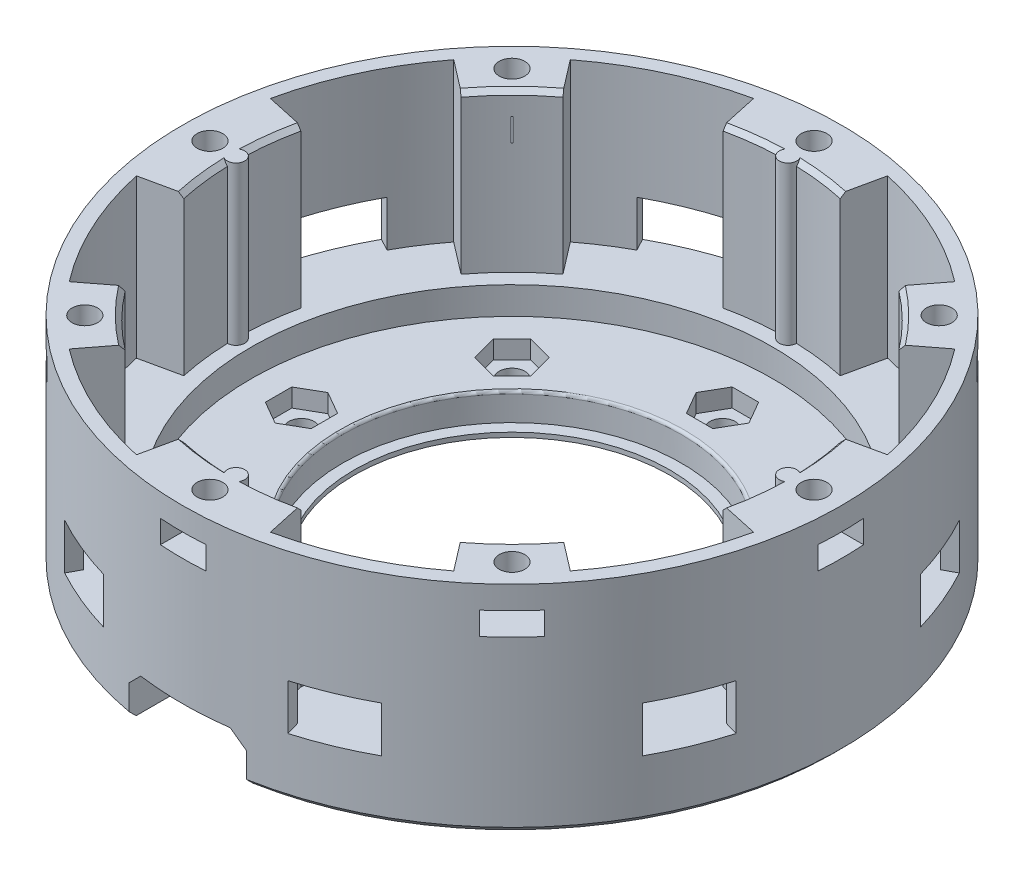
SolidWorks part; units mm, degrees
ref_plane "Front Plane" through (0, 0, 0) normal (0, 0, 1) x (1, 0, 0)
ref_plane "Top Plane" through (0, 0, 0) normal (0, 1, 0) x (1, 0, 0)
ref_plane "Right Plane" through (0, 0, 0) normal (1, 0, 0) x (0, 0, -1)
sketch "Sketch1" plane through (0, 0, 0) normal (0, 1, 0) x (1, 0, 0)
  circle A0 centre (0, 0) radius 36
  dimension "D1" = 72
extrude "Boss-Extrude1" add sketch "Sketch1" along normal blind 4
sketch "Sketch6" plane through (0, 4, 0) normal (0, 1, 0) x (1, 0, 0)
  circle A0 centre (0, 0) radius 16
  circle A1 centre (0, 0) radius 12.5
  dimension "D1" = 32
  dimension "D2" = 25
extrude "Boss-Extrude4" add sketch "Sketch6" along normal blind 0.3
sketch "Sketch7" plane through (0, 4.3, 0) normal (0, 1, 0) x (1, 0, 0)
  circle A0 centre (0, 0) radius 13.55
  circle A1 centre (0, 0) radius 16
  circle A2 centre (0, 0) radius 16
  dimension "D2" = 27.1
  dimension "D1" = 0
extrude "Boss-Extrude5" add sketch "Sketch7" along normal blind 4
sketch "Sketch2" plane through (0, 4, 0) normal (0, 1, 0) x (1, 0, 0)
  circle A0 centre (0, 0) radius 28.5
  circle A1 centre (0, 0) radius 36 construction
  circle A2 centre (0, 0) radius 36
  dimension "D1" = 57
extrude "Boss-Extrude2" add sketch "Sketch2" along normal offset from surface (5.8 mm away) 1.5 up to face at (0, 8.3, 16) offset beyond the face yes
sketch "Sketch3" plane through (0, 9.8, 0) normal (0, 1, 0) x (1, 0, 0)
  arc A0 (-0.9499, 30.135) -> (-30.135, 0.9499) centre (0, 0) ccw
  circle A1 centre (0, 0) radius 36 construction
  circle A2 centre (0, 0) radius 36
  arc A3 (-0.9499, 30.135) -> (0.9499, 30.135) centre (0, 30.15) ccw
  arc A4 (30.135, 0.9499) -> (30.135, -0.9499) centre (30.15, 0) ccw
  arc A5 (0.9499, -30.135) -> (-0.9499, -30.135) centre (0, -30.15) ccw
  arc A6 (-30.135, -0.9499) -> (-30.135, 0.9499) centre (-30.15, 0) ccw
  arc A7 (-30.135, -0.9499) -> (-0.9499, -30.135) centre (0, 0) ccw
  arc A8 (0.9499, -30.135) -> (30.135, -0.9499) centre (0, 0) ccw
  arc A9 (30.135, 0.9499) -> (0.9499, 30.135) centre (0, 0) ccw
  point P21 (0, 0)
  dimension "60.15" = 60.3
  dimension "D2" = 0.95
  dimension "D3" = 4
extrude "Boss-Extrude3" add sketch "Sketch3" along normal blind 17.25
sketch "Sketch8" plane through (0, 0, 0) normal (0, -1, 0) x (1, 0, 0)
  line L0 (0, 0) -> (0, -7.5) construction
  line L1 (-11, 7.5) -> (11, 7.5) construction
  line L2 (-11, 7.5) -> (-11, -7.5) construction
  line L3 (-11, -7.5) -> (11, -7.5) construction
  line L4 (11, 7.5) -> (11, -7.5) construction
  line L5 (-11, 7.5) -> (11, -7.5) construction
  line L6 (-11, -7.5) -> (11, 7.5) construction
  line L7 (0, 0) -> (11, 0) construction
  circle A0 centre (0, 0) radius 5.75
  circle A1 centre (-9, -5.5) radius 1.905
  circle A2 centre (9, -5.5) radius 1.905
  circle A3 centre (-9, 5.5) radius 1.905
  circle A4 centre (9, 5.5) radius 1.905
  point P0 (0, 0)
  dimension "D3" = 11.5
  dimension "D6" = 3.81
  dimension "D1" = 15
  dimension "D2" = 22
  dimension "D4" = 9
  dimension "D5" = 5.5
extrude "Cut-Extrude1" cut sketch "Sketch8" against normal up to surface (4 mm away) up to face at (0, 4, 16)
sketch "Sketch9" plane through (0, 0, 0) normal (0, -1, 0) x (1, 0, 0)
  line L0 (11, 7.5) -> (11, -7.5) construction
  line L1 (-11, -11) -> (11, -11)
  line L2 (-11, -11) -> (-11, -21)
  line L3 (-11, -21) -> (11, -21) construction
  line L4 (11, -11) -> (11, -21)
  line L5 (-11, 7.5) -> (11, 7.5) construction
  line L6 (-11, 7.5) -> (-11, -7.5) construction
  line L7 (0, 0) -> (0, -36) construction
  line L8 (-5, -27) -> (-5, -35.6511)
  line L9 (5, -27) -> (5, -35.6511)
  circle A0 centre (0, 0) radius 36 construction
  arc A1 (-11, -21) -> (-5, -27) centre (-11, -27) cw
  arc A2 (11, -21) -> (5, -27) centre (11, -27) ccw
  arc A3 (-5, -35.6511) -> (5, -35.6511) centre (0, 0) ccw
  dimension "D1" = 28.5
  dimension "D2" = 10
  dimension "D3" = 5
extrude "Cut-Extrude2" cut sketch "Sketch9" against normal blind 3
sketch "Sketch10" plane through (0, 4, 0) normal (0, 1, 0) x (1, 0, 0)
  circle A0 centre (0, 0) radius 16 construction
  circle A1 centre (0, 0) radius 28.5
  circle A2 centre (0, 0) radius 28.5
  circle A3 centre (0, 0) radius 16
  dimension "D1" = 0
extrude "Cut-Extrude3" cut sketch "Sketch10" against normal blind 2
sketch "Sketch11" plane through (0, 0, 0) normal (0, -1, 0) x (1, 0, 0)
  line L0 (-11, -11) -> (-11, -21) construction
  line L1 (11, -11) -> (-11, -11)
  line L2 (11, -11) -> (11, -10)
  line L3 (11, -10) -> (-11, -10)
  line L4 (-11, -11) -> (-11, -10)
  dimension "D1" = 1
sketch "Sketch12" plane through (0, 3, 0) normal (0, -1, 0) x (1, 0, 0)
  line L3 (11, -11.619) -> (11, -11)
  line L4 (11, -11) -> (-11, -11)
  line L5 (-11, -11) -> (-11, -11.619)
  line L6 (11, -11.619) -> (11, -11)
  line L7 (11, -11) -> (-11, -11)
  line L8 (-11, -11) -> (-11, -11.619)
  arc A1 (-11, -11.619) -> (11, -11.619) centre (0, 0) ccw
  arc A2 (-11, -11.619) -> (11, -11.619) centre (0, 0) ccw
  dimension "D1" = 0
loft "Loft1" add profiles "Sketch11", "Sketch12"
sketch "Sketch13" plane through (0, 27.05, 0) normal (0, 1, 0) x (1, 0, 0)
  line L0 (0, 0) -> (-25.4558, 25.4558) construction
  line L1 (-11, 7.5) -> (11, -7.5) construction
  line L2 (0, 0) -> (0, 36) construction
  line L3 (0, 0) -> (-7.6384, 35.1803) construction
  line L4 (0, 0) -> (-21.9154, 28.5607) construction
  line L5 (-21.0023, 27.3707) -> (-18.3542, 23.9196)
  line L6 (-7.3201, 33.7145) -> (-6.3972, 29.4635)
  line L7 (21.0023, 27.3707) -> (18.3542, 23.9196)
  line L8 (7.3201, 33.7145) -> (6.3972, 29.4635)
  line L9 (33.7145, 7.3201) -> (29.4635, 6.3972)
  line L10 (27.3707, 21.0023) -> (23.9196, 18.3542)
  line L11 (33.7145, -7.3201) -> (29.4635, -6.3972)
  line L12 (27.3707, -21.0023) -> (23.9196, -18.3542)
  line L13 (7.3201, -33.7145) -> (6.3972, -29.4635)
  line L14 (21.0023, -27.3707) -> (18.3542, -23.9196)
  line L15 (-7.3201, -33.7145) -> (-6.3972, -29.4635)
  line L16 (-21.0023, -27.3707) -> (-18.3542, -23.9196)
  line L17 (-33.7145, -7.3201) -> (-29.4635, -6.3972)
  line L18 (-27.3707, -21.0023) -> (-23.9196, -18.3542)
  line L19 (-33.7145, 7.3201) -> (-29.4635, 6.3972)
  line L20 (-27.3707, 21.0023) -> (-23.9196, 18.3542)
  circle A0 centre (0, 0) radius 36 construction
  arc A1 (-21.0023, 27.3707) -> (-7.3201, 33.7145) centre (0, 0) cw
  arc A2 (-0.9499, 30.135) -> (-30.135, 0.9499) centre (0, 0) ccw construction
  arc A3 (-18.3542, 23.9196) -> (-6.3972, 29.4635) centre (0, 0) cw
  arc A4 (21.0023, 27.3707) -> (7.3201, 33.7145) centre (0, 0) ccw
  arc A5 (18.3542, 23.9196) -> (6.3972, 29.4635) centre (0, 0) ccw
  arc A6 (23.9196, 18.3542) -> (29.4635, 6.3972) centre (0, 0) cw
  arc A7 (27.3707, 21.0023) -> (33.7145, 7.3201) centre (0, 0) cw
  arc A8 (27.3707, -21.0023) -> (33.7145, -7.3201) centre (0, 0) ccw
  arc A9 (23.9196, -18.3542) -> (29.4635, -6.3972) centre (0, 0) ccw
  arc A10 (18.3542, -23.9196) -> (6.3972, -29.4635) centre (0, 0) cw
  arc A11 (21.0023, -27.3707) -> (7.3201, -33.7145) centre (0, 0) cw
  arc A12 (-21.0023, -27.3707) -> (-7.3201, -33.7145) centre (0, 0) ccw
  arc A13 (-18.3542, -23.9196) -> (-6.3972, -29.4635) centre (0, 0) ccw
  arc A14 (-23.9196, -18.3542) -> (-29.4635, -6.3972) centre (0, 0) cw
  arc A15 (-27.3707, -21.0023) -> (-33.7145, -7.3201) centre (0, 0) cw
  arc A16 (-27.3707, 21.0023) -> (-33.7145, 7.3201) centre (0, 0) ccw
  arc A17 (-23.9196, 18.3542) -> (-29.4635, 6.3972) centre (0, 0) ccw
  point P50 (0, 0)
  dimension "D4" = 1.5
  dimension "D1" = 45
  dimension "D2" = 12.25
  dimension "D3" = 7.5
  dimension "D5" = 4
extrude "Cut-Extrude4" cut sketch "Sketch13" against normal up to surface (17.25 mm away) up to face at (0, 9.8, 28.5)
fillet "Fillet1" radius 3 2 edges at (0, 2, 16) (0, 2, 28.5)
chamfer "Chamfer3" distance 4 angle 45 1 edges at (0, 0, 36)
sketch "Sketch14" plane through (0, 2, 0) normal (0, 1, 0) x (1, 0, 0)
  line L0 (0, 0) -> (0, -25.5) construction
  line L1 (0, 0) -> (3.3284, -25.2818) construction
  line L2 (0, 0) -> (6.5999, -24.6311) construction
  line L3 (0, -25.5) -> (6.5999, -24.6311) construction
  line L4 (1.5, -18.9407) -> (1.5, -25.4558)
  line L5 (3.4533, -18.6835) -> (5.1396, -24.9767)
  line L6 (-1.5, -18.9407) -> (-1.5, -25.4558)
  line L7 (-3.4533, -18.6835) -> (-5.1396, -24.9767)
  line L8 (-6.3511, -17.9071) -> (-8.0373, -24.2002)
  line L9 (-8.1713, -17.1531) -> (-11.4289, -22.7954)
  line L10 (-10.7694, -15.6531) -> (-14.027, -21.2954)
  line L11 (-12.3324, -14.4538) -> (-16.9393, -19.0607)
  line L12 (-14.4538, -12.3324) -> (-19.0607, -16.9393)
  line L13 (-15.6531, -10.7694) -> (-21.2954, -14.027)
  line L14 (-17.1531, -8.1713) -> (-22.7954, -11.4289)
  line L15 (-17.9071, -6.3511) -> (-24.2002, -8.0373)
  line L16 (-18.6835, -3.4533) -> (-24.9767, -5.1396)
  line L17 (-18.9407, -1.5) -> (-25.4558, -1.5)
  line L18 (-18.9407, 1.5) -> (-25.4558, 1.5)
  line L19 (-18.6835, 3.4533) -> (-24.9767, 5.1396)
  line L20 (-17.9071, 6.3511) -> (-24.2002, 8.0373)
  line L21 (-17.1531, 8.1713) -> (-22.7954, 11.4289)
  line L22 (-15.6531, 10.7694) -> (-21.2954, 14.027)
  line L23 (-14.4538, 12.3324) -> (-19.0607, 16.9393)
  line L24 (-12.3324, 14.4538) -> (-16.9393, 19.0607) [skipped]
  line L25 (-10.7694, 15.6531) -> (-14.027, 21.2954) [skipped]
  line L26 (-8.1713, 17.1531) -> (-11.4289, 22.7954) [skipped]
  line L27 (-6.3511, 17.9071) -> (-8.0373, 24.2002) [skipped]
  line L28 (-3.4533, 18.6835) -> (-5.1396, 24.9767) [skipped]
  line L29 (-1.5, 18.9407) -> (-1.5, 25.4558) [skipped]
  line L30 (1.5, 18.9407) -> (1.5, 25.4558) [skipped]
  line L31 (3.4533, 18.6835) -> (5.1396, 24.9767) [skipped]
  line L32 (6.3511, 17.9071) -> (8.0373, 24.2002) [skipped]
  line L33 (8.1713, 17.1531) -> (11.4289, 22.7954) [skipped]
  line L34 (10.7694, 15.6531) -> (14.027, 21.2954) [skipped]
  line L35 (12.3324, 14.4538) -> (16.9393, 19.0607) [skipped]
  line L36 (14.4538, 12.3324) -> (19.0607, 16.9393)
  line L37 (15.6531, 10.7694) -> (21.2954, 14.027)
  line L38 (17.1531, 8.1713) -> (22.7954, 11.4289)
  line L39 (17.9071, 6.3511) -> (24.2002, 8.0373)
  line L40 (18.6835, 3.4533) -> (24.9767, 5.1396)
  line L41 (18.9407, 1.5) -> (25.4558, 1.5)
  line L42 (18.9407, -1.5) -> (25.4558, -1.5)
  line L43 (18.6835, -3.4533) -> (24.9767, -5.1396)
  line L44 (17.9071, -6.3511) -> (24.2002, -8.0373)
  line L45 (17.1531, -8.1713) -> (22.7954, -11.4289)
  line L46 (15.6531, -10.7694) -> (21.2954, -14.027)
  line L47 (14.4538, -12.3324) -> (19.0607, -16.9393)
  line L48 (12.3324, -14.4538) -> (16.9393, -19.0607)
  line L49 (10.7694, -15.6531) -> (14.027, -21.2954)
  line L50 (8.1713, -17.1531) -> (11.4289, -22.7954)
  line L51 (6.3511, -17.9071) -> (8.0373, -24.2002)
  arc A0 (-5.369, 24.9284) -> (5.369, 24.9284) centre (0, 0) ccw construction
  arc A1 (-11, 15.4919) -> (11, 15.4919) centre (0, 0) ccw construction
  arc A2 (1.5, -18.9407) -> (3.4533, -18.6835) centre (0, 0) ccw
  arc A3 (1.5, -25.4558) -> (5.1396, -24.9767) centre (0, 0) ccw
  arc A4 (-5.1396, -24.9767) -> (-1.5, -25.4558) centre (0, 0) ccw
  arc A5 (-3.4533, -18.6835) -> (-1.5, -18.9407) centre (0, 0) ccw
  arc A6 (-11.4289, -22.7954) -> (-8.0373, -24.2002) centre (0, 0) ccw
  arc A7 (-8.1713, -17.1531) -> (-6.3511, -17.9071) centre (0, 0) ccw
  arc A8 (-16.9393, -19.0607) -> (-14.027, -21.2954) centre (0, 0) ccw
  arc A9 (-12.3324, -14.4538) -> (-10.7694, -15.6531) centre (0, 0) ccw
  arc A10 (-21.2954, -14.027) -> (-19.0607, -16.9393) centre (0, 0) ccw
  arc A11 (-15.6531, -10.7694) -> (-14.4538, -12.3324) centre (0, 0) ccw
  arc A12 (-24.2002, -8.0373) -> (-22.7954, -11.4289) centre (0, 0) ccw
  arc A13 (-17.9071, -6.3511) -> (-17.1531, -8.1713) centre (0, 0) ccw
  arc A14 (-25.4558, -1.5) -> (-24.9767, -5.1396) centre (0, 0) ccw
  arc A15 (-18.9407, -1.5) -> (-18.6835, -3.4533) centre (0, 0) ccw
  arc A16 (-24.9767, 5.1396) -> (-25.4558, 1.5) centre (0, 0) ccw
  arc A17 (-18.6835, 3.4533) -> (-18.9407, 1.5) centre (0, 0) ccw
  arc A18 (-22.7954, 11.4289) -> (-24.2002, 8.0373) centre (0, 0) ccw
  arc A19 (-17.1531, 8.1713) -> (-17.9071, 6.3511) centre (0, 0) ccw
  arc A20 (-19.0607, 16.9393) -> (-21.2954, 14.027) centre (0, 0) ccw
  arc A21 (-14.4538, 12.3324) -> (-15.6531, 10.7694) centre (0, 0) ccw
  arc A22 (-14.027, 21.2954) -> (-16.9393, 19.0607) centre (0, 0) ccw [skipped]
  arc A23 (-10.7694, 15.6531) -> (-12.3324, 14.4538) centre (0, 0) ccw [skipped]
  arc A24 (-8.0373, 24.2002) -> (-11.4289, 22.7954) centre (0, 0) ccw [skipped]
  arc A25 (-6.3511, 17.9071) -> (-8.1713, 17.1531) centre (0, 0) ccw [skipped]
  arc A26 (-1.5, 25.4558) -> (-5.1396, 24.9767) centre (0, 0) ccw [skipped]
  arc A27 (-1.5, 18.9407) -> (-3.4533, 18.6835) centre (0, 0) ccw [skipped]
  arc A28 (5.1396, 24.9767) -> (1.5, 25.4558) centre (0, 0) ccw [skipped]
  arc A29 (3.4533, 18.6835) -> (1.5, 18.9407) centre (0, 0) ccw [skipped]
  arc A30 (11.4289, 22.7954) -> (8.0373, 24.2002) centre (0, 0) ccw [skipped]
  arc A31 (8.1713, 17.1531) -> (6.3511, 17.9071) centre (0, 0) ccw [skipped]
  arc A32 (16.9393, 19.0607) -> (14.027, 21.2954) centre (0, 0) ccw [skipped]
  arc A33 (12.3324, 14.4538) -> (10.7694, 15.6531) centre (0, 0) ccw [skipped]
  arc A34 (21.2954, 14.027) -> (19.0607, 16.9393) centre (0, 0) ccw
  arc A35 (15.6531, 10.7694) -> (14.4538, 12.3324) centre (0, 0) ccw
  arc A36 (24.2002, 8.0373) -> (22.7954, 11.4289) centre (0, 0) ccw
  arc A37 (17.9071, 6.3511) -> (17.1531, 8.1713) centre (0, 0) ccw
  arc A38 (25.4558, 1.5) -> (24.9767, 5.1396) centre (0, 0) ccw
  arc A39 (18.9407, 1.5) -> (18.6835, 3.4533) centre (0, 0) ccw
  arc A40 (24.9767, -5.1396) -> (25.4558, -1.5) centre (0, 0) ccw
  arc A41 (18.6835, -3.4533) -> (18.9407, -1.5) centre (0, 0) ccw
  arc A42 (22.7954, -11.4289) -> (24.2002, -8.0373) centre (0, 0) ccw
  arc A43 (17.1531, -8.1713) -> (17.9071, -6.3511) centre (0, 0) ccw
  arc A44 (19.0607, -16.9393) -> (21.2954, -14.027) centre (0, 0) ccw
  arc A45 (14.4538, -12.3324) -> (15.6531, -10.7694) centre (0, 0) ccw
  arc A46 (14.027, -21.2954) -> (16.9393, -19.0607) centre (0, 0) ccw
  arc A47 (10.7694, -15.6531) -> (12.3324, -14.4538) centre (0, 0) ccw
  arc A48 (8.0373, -24.2002) -> (11.4289, -22.7954) centre (0, 0) ccw
  arc A49 (6.3511, -17.9071) -> (8.1713, -17.1531) centre (0, 0) ccw
  point P9 (3.2999, -25.0656)
  point P88 (0, 0)
  point P113 (0, 0)
  dimension "D1" = 15
  dimension "D2" = 1.5
  dimension "D3" = 24
extrude "Cut-Extrude5" cut sketch "Sketch14" against normal through all
sketch "Sketch15" plane through (0, 27.05, 0) normal (0, 1, 0) x (1, 0, 0)
  circle A0 centre (0, 33) radius 1.4
  circle A1 centre (0, 0) radius 36 construction
  circle A2 centre (23.3345, 23.3345) radius 1.4
  circle A3 centre (33, 0) radius 1.4
  circle A4 centre (23.3345, -23.3345) radius 1.4
  circle A5 centre (0, -33) radius 1.4
  circle A6 centre (-23.3345, -23.3345) radius 1.4
  circle A7 centre (-33, 0) radius 1.4
  circle A8 centre (-23.3345, 23.3345) radius 1.4
  point P5 (0, 36)
  point P23 (0, 0)
  dimension "D1" = 2.8
  dimension "D2" = 3
  dimension "D3" = 8
extrude "Cut-Extrude6" cut sketch "Sketch15" against normal blind 5
chamfer "Chamfer4" distance 0.3 angle 45 1 edges at (0, 4, 5.75)
sketch "Sketch16" plane through (0, 3, 0) normal (0, -1, 0) x (1, 0, 0)
  line L0 (-5, -28.058) -> (-5, -34.641) construction
  line L1 (5, -28.058) -> (-5, -28.058)
  line L2 (5, -28.058) -> (5, -36)
  line L3 (5, -36) -> (-5, -36)
  line L4 (-5, -28.058) -> (-5, -36)
  circle A0 centre (0, 0) radius 36 construction
extrude "Cut-Extrude7" cut sketch "Sketch16" against normal blind 2
chamfer "Chamfer5" distance 0.5 angle 45 12 edges at (-21.3193, 27.05, 21.3193) (-3.6888, 27.05, 29.9235) (3.6888, 27.05, 29.9235) (21.3193, 27.05, 21.3193) (29.9235, 27.05, 3.6888) (29.9235, 27.05, -3.6888) (21.3193, 27.05, -21.3193) (3.6888, 27.05, -29.9235) (-3.6888, 27.05, -29.9235) (-21.3193, 27.05, -21.3193) (-29.9235, 27.05, 3.6888) (-29.9235, 27.05, -3.6888)
sketch "Sketch17" plane through (0, 9.8, 0) normal (0, 1, 0) x (1, 0, 0)
  line L0 (-17.3102, 31.5651) -> (-16.5889, 30.2499)
  line L1 (-9.6598, 33.1201) -> (-10.0798, 34.5601)
  line L2 (0, 0) -> (0, 36) construction
  line L3 (0, 0) -> (-13.2026, 31.8738) construction
  line L4 (10.0798, 34.5601) -> (9.6598, 33.1201)
  line L5 (16.5889, 30.2499) -> (17.3102, 31.5651)
  line L6 (31.5651, 17.3102) -> (30.2499, 16.5889)
  line L7 (33.1201, 9.6598) -> (34.5601, 10.0798)
  line L8 (34.5601, -10.0798) -> (33.1201, -9.6598)
  line L9 (30.2499, -16.5889) -> (31.5651, -17.3102)
  line L10 (17.3102, -31.5651) -> (16.5889, -30.2499)
  line L11 (9.6598, -33.1201) -> (10.0798, -34.5601)
  line L12 (-10.0798, -34.5601) -> (-9.6598, -33.1201)
  line L13 (-16.5889, -30.2499) -> (-17.3102, -31.5651)
  line L14 (-31.5651, -17.3102) -> (-30.2499, -16.5889)
  line L15 (-33.1201, -9.6598) -> (-34.5601, -10.0798)
  line L16 (-34.5601, 10.0798) -> (-33.1201, 9.6598)
  line L17 (-30.2499, 16.5889) -> (-31.5651, 17.3102)
  arc A0 (-16.5889, 30.2499) -> (-9.6598, 33.1201) centre (0, 0) cw
  arc A1 (-7.3201, 33.7145) -> (-21.0023, 27.3707) centre (0, 0) ccw construction
  arc A2 (-17.3102, 31.5651) -> (-10.0798, 34.5601) centre (0, 0) cw
  circle A3 centre (0, 0) radius 36 construction
  arc A4 (-7.3201, 33.7145) -> (-21.0023, 27.3707) centre (0, 0) ccw construction
  arc A5 (9.6598, 33.1201) -> (16.5889, 30.2499) centre (0, 0) cw
  arc A6 (10.0798, 34.5601) -> (17.3102, 31.5651) centre (0, 0) cw
  arc A7 (30.2499, 16.5889) -> (33.1201, 9.6598) centre (0, 0) cw
  arc A8 (31.5651, 17.3102) -> (34.5601, 10.0798) centre (0, 0) cw
  arc A9 (33.1201, -9.6598) -> (30.2499, -16.5889) centre (0, 0) cw
  arc A10 (34.5601, -10.0798) -> (31.5651, -17.3102) centre (0, 0) cw
  arc A11 (16.5889, -30.2499) -> (9.6598, -33.1201) centre (0, 0) cw
  arc A12 (17.3102, -31.5651) -> (10.0798, -34.5601) centre (0, 0) cw
  arc A13 (-9.6598, -33.1201) -> (-16.5889, -30.2499) centre (0, 0) cw
  arc A14 (-10.0798, -34.5601) -> (-17.3102, -31.5651) centre (0, 0) cw
  arc A15 (-30.2499, -16.5889) -> (-33.1201, -9.6598) centre (0, 0) cw
  arc A16 (-31.5651, -17.3102) -> (-34.5601, -10.0798) centre (0, 0) cw
  arc A17 (-33.1201, 9.6598) -> (-30.2499, 16.5889) centre (0, 0) cw
  arc A18 (-34.5601, 10.0798) -> (-31.5651, 17.3102) centre (0, 0) cw
  point P48 (0, 0)
  dimension "D1" = 22.5
  dimension "D2" = 7.5
  dimension "D3" = 8
extrude "Cut-Extrude8" cut sketch "Sketch17" along normal blind 5
sketch "Sketch18" plane through (0, 22.05, 0) normal (0, 1, 0) x (1, 0, 0)
  line L0 (-2.5, 34.4434) -> (-2.5, 36)
  line L1 (0, 35.8868) -> (-2.5, 34.4434) construction
  line L2 (-2.5, 34.4434) -> (-2.5, 31.5566)
  line L3 (-2.5, 31.5566) -> (0, 30.1132)
  line L4 (0, 30.1132) -> (2.5, 31.5566)
  line L5 (2.5, 31.5566) -> (2.5, 34.4434)
  line L6 (2.5, 34.4434) -> (0, 35.8868) construction
  line L7 (-2.5, 36) -> (2.5, 36)
  line L8 (2.5, 36) -> (2.5, 34.4434)
  line L9 (23.6881, 27.2236) -> (27.2236, 23.6881)
  line L10 (27.2236, 23.6881) -> (26.1229, 22.5874)
  line L11 (24.0817, 20.5461) -> (26.1229, 22.5874)
  line L12 (21.2933, 21.2933) -> (24.0817, 20.5461)
  line L13 (20.5461, 24.0817) -> (21.2933, 21.2933)
  line L14 (22.5874, 26.1229) -> (20.5461, 24.0817)
  line L15 (22.5874, 26.1229) -> (23.6881, 27.2236)
  line L16 (36, 2.5) -> (36, -2.5)
  line L17 (36, -2.5) -> (34.4434, -2.5)
  line L18 (31.5566, -2.5) -> (34.4434, -2.5)
  line L19 (30.1132, 0) -> (31.5566, -2.5)
  line L20 (31.5566, 2.5) -> (30.1132, 0)
  line L21 (34.4434, 2.5) -> (31.5566, 2.5)
  line L22 (34.4434, 2.5) -> (36, 2.5)
  line L23 (27.2236, -23.6881) -> (23.6881, -27.2236)
  line L24 (23.6881, -27.2236) -> (22.5874, -26.1229)
  line L25 (20.5461, -24.0817) -> (22.5874, -26.1229)
  line L26 (21.2933, -21.2933) -> (20.5461, -24.0817)
  line L27 (24.0817, -20.5461) -> (21.2933, -21.2933)
  line L28 (26.1229, -22.5874) -> (24.0817, -20.5461)
  line L29 (26.1229, -22.5874) -> (27.2236, -23.6881)
  line L30 (2.5, -36) -> (-2.5, -36)
  line L31 (-2.5, -36) -> (-2.5, -34.4434)
  line L32 (-2.5, -31.5566) -> (-2.5, -34.4434)
  line L33 (0, -30.1132) -> (-2.5, -31.5566)
  line L34 (2.5, -31.5566) -> (0, -30.1132)
  line L35 (2.5, -34.4434) -> (2.5, -31.5566)
  line L36 (2.5, -34.4434) -> (2.5, -36)
  line L37 (-23.6881, -27.2236) -> (-27.2236, -23.6881)
  line L38 (-27.2236, -23.6881) -> (-26.1229, -22.5874)
  line L39 (-24.0817, -20.5461) -> (-26.1229, -22.5874)
  line L40 (-21.2933, -21.2933) -> (-24.0817, -20.5461)
  line L41 (-20.5461, -24.0817) -> (-21.2933, -21.2933)
  line L42 (-22.5874, -26.1229) -> (-20.5461, -24.0817)
  line L43 (-22.5874, -26.1229) -> (-23.6881, -27.2236)
  line L44 (-36, -2.5) -> (-36, 2.5)
  line L45 (-36, 2.5) -> (-34.4434, 2.5)
  line L46 (-31.5566, 2.5) -> (-34.4434, 2.5)
  line L47 (-30.1132, 0) -> (-31.5566, 2.5)
  line L48 (-31.5566, -2.5) -> (-30.1132, 0)
  line L49 (-34.4434, -2.5) -> (-31.5566, -2.5)
  line L50 (-34.4434, -2.5) -> (-36, -2.5)
  line L51 (-27.2236, 23.6881) -> (-23.6881, 27.2236)
  line L52 (-23.6881, 27.2236) -> (-22.5874, 26.1229)
  line L53 (-20.5461, 24.0817) -> (-22.5874, 26.1229)
  line L54 (-21.2933, 21.2933) -> (-20.5461, 24.0817)
  line L55 (-24.0817, 20.5461) -> (-21.2933, 21.2933)
  line L56 (-26.1229, 22.5874) -> (-24.0817, 20.5461)
  line L57 (-26.1229, 22.5874) -> (-27.2236, 23.6881)
  circle A0 centre (0, 33) radius 2.5 construction
  circle A1 centre (0, 0) radius 36 construction
  point P65 (0, 0)
  dimension "D1" = 5
  dimension "D2" = 8
extrude "Cut-Extrude9" cut sketch "Sketch18" along normal blind 2.5
sketch "Sketch19" plane through (0, 0, 0) normal (0, -1, 0) x (1, 0, 0)
  line L1 (-3.05, -1.833) -> (5.45, -1.833)
  line L2 (-3.05, -1.833) -> (-3.05, -16)
  line L3 (-3.05, -16) -> (5.45, -16)
  line L4 (5.45, -1.833) -> (5.45, -16)
  circle A0 centre (0, 0) radius 5.75 construction
  arc A1 (-11, -11.619) -> (11, -11.619) centre (0, 0) ccw construction
  point P8 (1.2, -1.833)
  dimension "D1" = 8.5
  dimension "D2" = 1.2
extrude "Cut-Extrude10" cut sketch "Sketch19" against normal blind 2
ref_plane "Plane1" through (0, 6.8, 0) normal (0, 1, 0) x (1, 0, 0)
sketch "Sketch20" plane through (0, 6.8, 0) normal (0, 1, 0) x (1, 0, 0)
  circle A0 centre (0, 0) radius 36
extrude "Cut-Extrude11" cut sketch "Sketch20" against normal blind 10
sketch "Sketch21" plane through (0, 6.8, 0) normal (0, -1, 0) x (1, 0, 0)
  line L0 (0, 0) -> (0, 36) construction
  circle A0 centre (0, 0) radius 36 construction
sketch "Sketch23" plane through (0, 6.8, 0) normal (0, -1, 0) x (1, 0, 0)
  line L0 (0, 0) -> (0, -17.25) construction
  line L1 (-1, -17.221) -> (-1, -27.3875)
  line L2 (-1, -27.3875) -> (-4, -27.3875)
  line L3 (-4, -27.3875) -> (-4, -21.8875)
  line L4 (-19.2691, -11.125) -> (-21.0011, -12.125)
  line L5 (-8.5, -22.7115) -> (-8.5, -27.2029)
  line L6 (-8.5, -27.2029) -> (8.5, -27.2029) construction
  line L7 (19.2691, -11.125) -> (21.0011, -12.125)
  line L8 (8.5, -22.7115) -> (8.5, -27.2029)
  line L9 (4, -27.3875) -> (4, -21.8875) construction
  line L10 (1, -27.3875) -> (4, -27.3875)
  line L11 (1, -17.221) -> (1, -27.3875)
  line L12 (4, -27.3875) -> (6, -27.3875)
  line L13 (6, -27.3875) -> (6, -21.4257)
  circle A0 centre (0, 0) radius 36 construction
  circle A1 centre (0, 0) radius 36
  circle A2 centre (0, 0) radius 17.25 construction
  arc A3 (-4, -21.8875) -> (-19.2691, -11.125) centre (0, 0) cw
  arc A4 (-21.0011, -12.125) -> (-8.5, -22.7115) centre (0, 0) ccw
  arc A5 (21.0011, -12.125) -> (8.5, -22.7115) centre (0, 0) cw
  arc A6 (4, -21.8875) -> (19.2691, -11.125) centre (0, 0) ccw construction
  arc A7 (-1, -17.221) -> (1, -17.221) centre (0, 0) cw
  circle A8 centre (0, 0) radius 28.5 construction
  arc A9 (6, -21.4257) -> (19.2691, -11.125) centre (0, 0) ccw
  arc A10 (-8.5, -27.2029) -> (8.5, -27.2029) centre (0, 0) ccw
  point P19 (0, -27.2029)
  point P26 (-8.4147, -22.5029)
  point P29 (8.975, -27.0499)
  point P30 (-8.5, -27.3875)
  point P31 (-8.5, -29.4577)
  point P32 (-8.5, -27.2029)
  dimension "D1" = 34.5
  dimension "D4" = 5
  dimension "D7" = 2
  dimension "D2" = 2
  dimension "D3" = 5.5
  dimension "D5" = 8
  dimension "D6" = 2
  dimension "D8" = 2.5
  dimension "D9" = 60
extrude "Boss-Extrude6" [suppressed] add sketch "Sketch23" along normal blind 5
sketch "Sketch25" [suppressed] plane through (0, 6.8, 0) normal (0, 1, 0) x (1, 0, 0)
  circle A0 centre (0, 0) radius 18.55
  dimension "D1" = 37.1
extrude "Cut-Extrude12" [suppressed] cut sketch "Sketch25" against normal blind 3
sketch "Sketch26" [suppressed] plane through (6, 0, 0) normal (1, 0, 0) x (0, 0, -1)
  line L0 (24.4066, 1.8) -> (24.4066, 6.8) construction
  line L1 (21.4257, 1.8) -> (27.3875, 1.8) construction
  line L2 (21.4257, 6.8) -> (27.3875, 6.8) construction
  circle A0 centre (24.4066, 4.3) radius 1.9304
  dimension "D1" = 3.8608
extrude "Cut-Extrude13" [suppressed] cut sketch "Sketch26" against normal up to surface (5 mm away)
ref_plane "Plane2" through (-6.5, 0, 0) normal (1, 0, 0) x (0, 0, -1)
sketch "Sketch27" [suppressed] plane through (-6.5, 0, 0) normal (1, 0, 0) x (0, 0, -1)
  line L0 (21.4762, 4.3) -> (21.4762, 0.3)
  line L1 (21.4762, 0.3) -> (27.337, 0.3)
  line L2 (27.337, 0.3) -> (27.337, 4.3)
  circle A0 centre (24.4066, 4.3) radius 1.9304 construction
  circle A1 centre (24.4066, 4.3) radius 1.9304 construction
  circle A2 centre (24.4066, 4.3) radius 2.9304 construction
  arc A3 (21.4762, 4.3) -> (27.337, 4.3) centre (24.4066, 4.3) cw
  point P6 (24.4066, 4.3)
  point P11 (27.3312, 4.4839)
  dimension "D2" = 4
  dimension "D1" = 1
ref_plane "Plane3" [suppressed] through (0, 0, -24.4066) normal (0, 0, 1) x (1, 0, 0)
sketch "Sketch28" [suppressed] plane through (0, 0, -24.4066) normal (0, 0, 1) x (1, 0, 0)
  line L0 (-6.5, 4.3) -> (-26.409, -2.9463)
  line L3 (-6.5, 2.3696) -> (-6.5, 6.2304) construction
  point P4 (0, 0)
  point P5 (-31.9816, -2.5278)
  point P6 (-26.9648, -1.1835)
  dimension "D1" = 70
sweep "Cut-Sweep1" [suppressed] cut profiles "Sketch27" path "Sketch28"
mirror "Mirror1" [suppressed] about plane through (0, 0, 0) normal (1, 0, 0)
sketch "Sketch29" [suppressed] plane through (-4, 0, 0) normal (-1, 0, 0) x (0, 0, 1)
  circle A0 centre (-24.4066, 4.3) radius 1.35
  circle A1 centre (-24.4066, 4.3) radius 1.9304 construction
  dimension "D1" = 2.7
extrude "Cut-Extrude14" [suppressed] cut sketch "Sketch29" against normal up to surface (3 mm away)
sketch "Sketch30" [suppressed] plane through (0, 1.8, 0) normal (0, -1, 0) x (1, 0, 0)
  line L0 (-19.799, 19.799) -> (0, 0) construction
  line L1 (0, 0) -> (0, 36) construction
  line L2 (0, 0) -> (-19.799, 19.799) construction
  line L3 (0, 0) -> (-28, 0) construction
  line L4 (0, 0) -> (0, 36) construction
  circle A0 centre (0, 0) radius 28 construction
  circle A1 centre (-19.799, 19.799) radius 1.9304
  circle A2 centre (-28, 0) radius 1.9304
  circle A3 centre (-19.799, -19.799) radius 1.9304
  circle A4 centre (19.799, -19.799) radius 1.9304
  circle A5 centre (19.799, 19.799) radius 1.9304
  circle A6 centre (28, 0) radius 1.9304
  dimension "D1" = 56
  dimension "D2" = 3.8608
  dimension "D3" = 45
  dimension "D5" = 45
  dimension "D4" = 3
extrude "Cut-Extrude15" [suppressed] cut sketch "Sketch30" against normal blind 3.5
sketch "Sketch31" plane through (0, 6.8, 0) normal (0, -1, 0) x (1, 0, 0)
  circle A0 centre (0, 0) radius 36
  circle A1 centre (0, 0) radius 36 construction
  circle A2 centre (0, 0) radius 17.25
  dimension "D1" = 34.5
extrude "Boss-Extrude7" add sketch "Sketch31" along normal blind 3.5
sketch "Sketch32" plane through (0, 6.8, 0) normal (0, 1, 0) x (1, 0, 0)
  circle A0 centre (0, 0) radius 18.525
  dimension "D1" = 37.05
extrude "Cut-Extrude16" cut sketch "Sketch32" against normal blind 3
fillet "Fillet2" radius 0.3 1 edges at (0, 6.8, 18.525)
sketch "Sketch33" plane through (0, 3.3, 0) normal (0, -1, 0) x (1, 0, 0)
  line L0 (-16.2635, 16.2635) -> (0, 0) construction
  line L1 (0, 0) -> (0, 36) construction
  line L2 (0, 0) -> (-16.2635, 16.2635) construction
  line L3 (0, 0) -> (-23, 0) construction
  circle A0 centre (0, 0) radius 23 construction
  circle A1 centre (-16.2635, 16.2635) radius 1.4
  circle A2 centre (-23, 0) radius 1.4
  circle A3 centre (-16.2635, -16.2635) radius 1.4
  circle A4 centre (16.2635, -16.2635) radius 1.4
  circle A5 centre (23, 0) radius 1.4
  circle A6 centre (16.2635, 16.2635) radius 1.4
  circle A8 centre (0, -23) radius 1.4
  dimension "D1" = 46
  dimension "D2" = 2.8
  dimension "D3" = 45
  dimension "D5" = 45
  dimension "D4" = 3
extrude "Cut-Extrude17" cut sketch "Sketch33" against normal blind 3.5
sketch "Sketch34" plane through (0, 6.8, 0) normal (0, 1, 0) x (1, 0, 0)
  line L0 (0, 0) -> (-16.2635, 16.2635) construction
  line L1 (1.4434, 20.5) -> (2.8868, 23)
  line L2 (-13.4751, 15.5163) -> (-14.2222, 18.3047)
  line L3 (-14.2222, 18.3047) -> (-17.0106, 19.0518)
  line L4 (-17.0106, 19.0518) -> (-19.0518, 17.0106)
  line L5 (-19.0518, 17.0106) -> (-18.3047, 14.2222)
  line L6 (-18.3047, 14.2222) -> (-15.5163, 13.4751)
  line L7 (-15.5163, 13.4751) -> (-13.4751, 15.5163)
  line L8 (2.8868, 23) -> (1.4434, 25.5)
  line L9 (1.4434, 25.5) -> (-1.4434, 25.5)
  line L10 (-1.4434, 25.5) -> (-2.8868, 23)
  line L11 (-2.8868, 23) -> (-1.4434, 20.5)
  line L12 (-1.4434, 20.5) -> (1.4434, 20.5)
  line L79 (15.5163, 13.4751) -> (18.3047, 14.2222)
  line L80 (18.3047, 14.2222) -> (19.0518, 17.0106)
  line L81 (19.0518, 17.0106) -> (17.0106, 19.0518)
  line L82 (17.0106, 19.0518) -> (14.2222, 18.3047)
  line L83 (14.2222, 18.3047) -> (13.4751, 15.5163)
  line L84 (13.4751, 15.5163) -> (15.5163, 13.4751)
  line L85 (20.5, -1.4434) -> (23, -2.8868)
  line L86 (23, -2.8868) -> (25.5, -1.4434)
  line L87 (25.5, -1.4434) -> (25.5, 1.4434)
  line L88 (25.5, 1.4434) -> (23, 2.8868)
  line L89 (23, 2.8868) -> (20.5, 1.4434)
  line L90 (20.5, 1.4434) -> (20.5, -1.4434)
  line L91 (13.4751, -15.5163) -> (14.2222, -18.3047)
  line L92 (14.2222, -18.3047) -> (17.0106, -19.0518)
  line L93 (17.0106, -19.0518) -> (19.0518, -17.0106)
  line L94 (19.0518, -17.0106) -> (18.3047, -14.2222)
  line L95 (18.3047, -14.2222) -> (15.5163, -13.4751)
  line L96 (15.5163, -13.4751) -> (13.4751, -15.5163)
  line L97 (-1.4434, -20.5) -> (-2.8868, -23) [skipped]
  line L98 (-2.8868, -23) -> (-1.4434, -25.5) [skipped]
  line L99 (-1.4434, -25.5) -> (1.4434, -25.5) [skipped]
  line L100 (1.4434, -25.5) -> (2.8868, -23) [skipped]
  line L101 (2.8868, -23) -> (1.4434, -20.5) [skipped]
  line L102 (1.4434, -20.5) -> (-1.4434, -20.5) [skipped]
  line L103 (-15.5163, -13.4751) -> (-18.3047, -14.2222)
  line L104 (-18.3047, -14.2222) -> (-19.0518, -17.0106)
  line L105 (-19.0518, -17.0106) -> (-17.0106, -19.0518)
  line L106 (-17.0106, -19.0518) -> (-14.2222, -18.3047)
  line L107 (-14.2222, -18.3047) -> (-13.4751, -15.5163)
  line L108 (-13.4751, -15.5163) -> (-15.5163, -13.4751)
  line L109 (-20.5, 1.4434) -> (-23, 2.8868)
  line L110 (-23, 2.8868) -> (-25.5, 1.4434)
  line L111 (-25.5, 1.4434) -> (-25.5, -1.4434)
  line L112 (-25.5, -1.4434) -> (-23, -2.8868)
  line L113 (-23, -2.8868) -> (-20.5, -1.4434)
  line L114 (-20.5, -1.4434) -> (-20.5, 1.4434)
  circle A0 centre (-16.2635, 16.2635) radius 2.5 construction
  point P4 (0, 0)
  point P12 (0, 0)
  point P56 (0, 0)
  dimension "D1" = 5
  dimension "D2" = 8
extrude "Cut-Extrude18" cut sketch "Sketch34" against normal blind 2
chamfer "Chamfer7" distance 0.75 angle 45 1 edges at (0, 3.3, -36)
sketch "Sketch35" plane through (0, 3.3, 0) normal (0, -1, 0) x (1, 0, 0)
  line L0 (-11, 20.5) -> (11, 20.5) construction
  line L1 (-11, 20.5) -> (11, 20.5) construction
  line L4 (-11, 20.5) -> (-11, 13.2877)
  line L5 (11, 20.5) -> (11, 13.2877)
  line L6 (-11, 20.5) -> (-6.3972, 25.5)
  line L7 (-6.3972, 25.5) -> (6.3972, 25.5)
  line L8 (6.3972, 25.5) -> (11, 20.5)
  circle A0 centre (0, 0) radius 17.25 construction
  arc A1 (-11, 13.2877) -> (11, 13.2877) centre (0, 0) cw
  point P2 (0, 25.5)
  point P11 (-3.6217, 26.9231)
  point P12 (0, 0)
  dimension "D2" = 5
extrude "Cut-Extrude19" cut sketch "Sketch35" against normal blind 2 contours L5 A1 L4 L6 L7 L8
sketch "Sketch36" plane through (0, 6.8, 0) normal (0, 1, 0) x (1, 0, 0)
  line L0 (-6.3972, -25.5) -> (6.3972, -25.5) construction
  line L1 (-6.3972, -25.5) -> (6.3972, -25.5)
  line L2 (-6.3972, -25.5) -> (-6.3972, -29.4635)
  line L3 (6.3972, -25.5) -> (6.3972, -29.4635)
  arc A0 (0.9499, -30.135) -> (6.3972, -29.4635) centre (0, 0) ccw construction
  arc A1 (0.9499, -30.135) -> (-0.9499, -30.135) centre (0, -30.15) ccw construction
  arc A2 (-6.3972, -29.4635) -> (-0.9499, -30.135) centre (0, 0) ccw construction
  arc A3 (0.9499, -30.135) -> (6.3972, -29.4635) centre (0, 0) ccw
  arc A4 (0.9499, -30.135) -> (-0.9499, -30.135) centre (0, -30.15) ccw
  arc A5 (-6.3972, -29.4635) -> (-0.9499, -30.135) centre (0, 0) ccw
extrude "Cut-Extrude20" cut sketch "Sketch36" against normal through all both and the other way through all
sketch "Sketch37" plane through (0, 3.3, 0) normal (0, -1, 0) x (1, 0, 0)
  line L0 (6.3972, 29.4635) -> (6.3972, 25.5) construction
  line L1 (-6.3972, 29.2) -> (6.3972, 29.2)
  line L2 (-6.3972, 29.2) -> (-6.3972, 39.2)
  line L3 (-6.3972, 39.2) -> (6.3972, 39.2)
  line L4 (6.3972, 29.2) -> (6.3972, 39.2)
  line L5 (-6.3972, 25.5) -> (-6.3972, 29.4635) construction
  arc A0 (-0.9499, 30.135) -> (0.9499, 30.135) centre (0, 30.15) ccw construction
  point P8 (-6.3972, 28.3785)
  dimension "D1" = 10
extrude "Cut-Extrude21" cut sketch "Sketch37" against normal blind 5
chamfer "Chamfer8" distance 1.5 angle 45 2 edges at (-6.3972, 8.3, 32.4453) (6.3972, 8.3, 32.4453)
sketch "Sketch38" plane through (0, 5.3, 0) normal (0, -1, 0) x (1, 0, 0)
  line L1 (1.8764, 26.25) -> (-1.8764, 26.25)
  line L2 (-1.8764, 26.25) -> (-3.7528, 23)
  line L3 (-3.7528, 23) -> (-1.8764, 19.75)
  line L4 (-1.8764, 19.75) -> (1.8764, 19.75)
  line L5 (1.8764, 19.75) -> (3.7528, 23)
  line L6 (3.7528, 23) -> (1.8764, 26.25)
  circle A0 centre (0, 0) radius 23 construction
  circle A1 centre (0, 23) radius 3.25 construction
  point P4 (-1.9529, 26.3825)
  dimension "D1" = 46
  dimension "D2" = 6.5
extrude "Boss-Extrude8" add sketch "Sketch38" along normal up to surface (2 mm away) contours L5 L6 L1 L2 L3 L4 up to face at (0, 3.3, 10.9315)
sketch "Sketch39" plane through (0, 6.8, 0) normal (0, 1, 0) x (1, 0, 0)
  line L0 (15.5163, -13.4751) -> (13.4751, -15.5163) construction
  line L1 (1.4434, -25.5) -> (2.8868, -23)
  line L2 (2.8868, -23) -> (1.4434, -20.5)
  line L3 (1.4434, -20.5) -> (-1.4434, -20.5)
  line L4 (-1.4434, -20.5) -> (-2.8868, -23)
  line L5 (-2.8868, -23) -> (-1.4434, -25.5)
  line L6 (-1.4434, -25.5) -> (1.4434, -25.5)
  circle A0 centre (0, 0) radius 23 construction
  circle A1 centre (0, 0) radius 23 construction
  circle A2 centre (0, -23) radius 2.5 construction
extrude "Cut-Extrude22" cut sketch "Sketch39" against normal blind 2
sketch "Sketch40" plane through (0, 5.3, 0) normal (0, 1, 0) x (1, 0, 0)
  line L6 (1.8764, -26.25) -> (2.3094, -25.5)
  line L7 (2.3094, -25.5) -> (1.4434, -25.5)
  line L8 (1.4434, -25.5) -> (-1.4434, -25.5)
  line L9 (-1.4434, -25.5) -> (-2.3094, -25.5)
  line L10 (-2.3094, -25.5) -> (-1.8764, -26.25)
  line L11 (-1.8764, -26.25) -> (1.8764, -26.25)
  line L12 (1.8764, -26.25) -> (2.3094, -25.5)
  line L13 (2.3094, -25.5) -> (1.4434, -25.5)
  line L14 (1.4434, -25.5) -> (-1.4434, -25.5)
  line L15 (-1.4434, -25.5) -> (-2.3094, -25.5)
  line L16 (-2.3094, -25.5) -> (-1.8764, -26.25)
  line L17 (-1.8764, -26.25) -> (1.8764, -26.25)
  dimension "D1" = 0
extrude "Cut-Extrude23" cut sketch "Sketch40" against normal through all
chamfer "Chamfer9" distance 2 angle 45 2 edges at (2.8146, 5.3, 21.375) (-2.8146, 5.3, 21.375)
sketch "Sketch41" plane through (0, 3.3, 0) normal (0, -1, 0) x (1, 0, 0)
  circle A0 centre (0, 23) radius 1.4
  circle A1 centre (16.2635, 16.2635) radius 1.4 construction
extrude "Cut-Extrude24" cut sketch "Sketch41" against normal through all both and the other way through all
